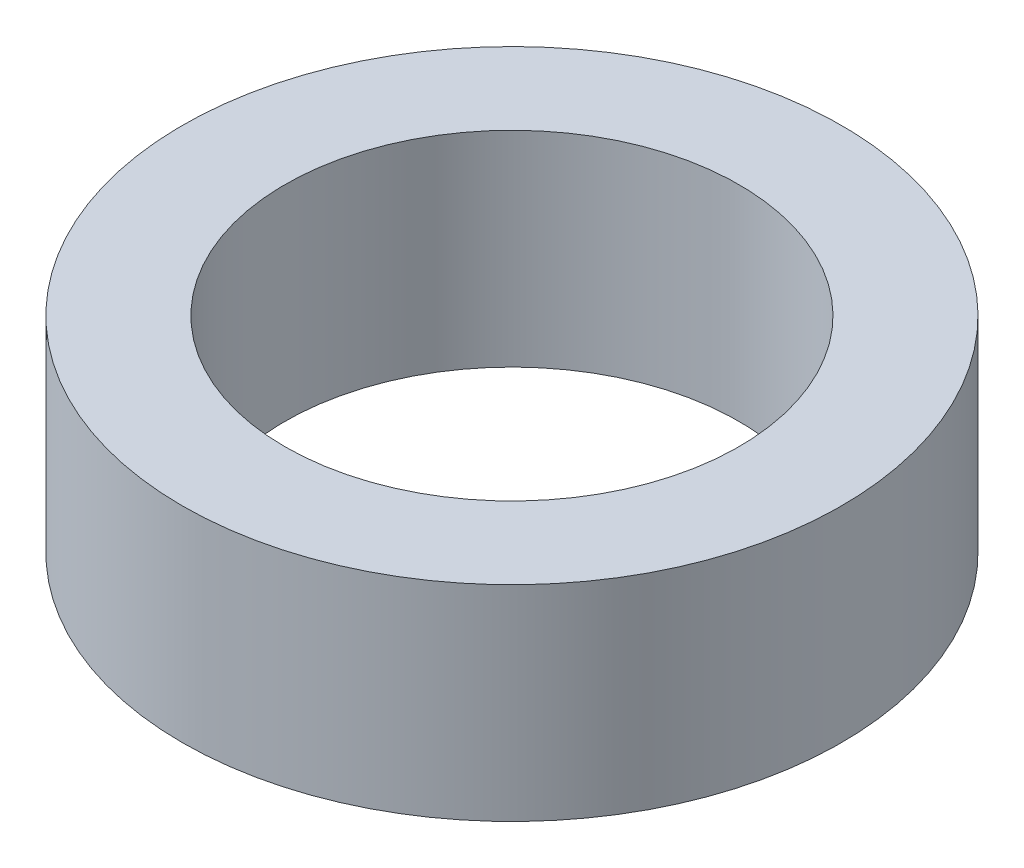
SolidWorks part; units mm, degrees
ref_plane "Front Plane" through (0, 0, 0) normal (0, 0, 1) x (1, 0, 0)
ref_plane "Top Plane" through (0, 0, 0) normal (0, 1, 0) x (1, 0, 0)
ref_plane "Right Plane" through (0, 0, 0) normal (1, 0, 0) x (0, 0, -1)
sketch "Axle Tension Bearing" plane through (0, 0, 0) normal (0, 1, 0) x (1, 0, 0)
  circle A0 centre (0, 0) radius 7.0301
  circle A1 centre (0, 0) radius 10.2051
  dimension "D1" = 14.0603
  dimension "D2" = 20.4103
extrude "Boss-Extrude1" add sketch "Axle Tension Bearing" along normal blind 6.35 contours A1 A0 region at (-9.9165, 0, 0)
equation "\"Ball Diameter\"= 1.75in"
equation "\"Sheet Thickness\"= 0.25in"
equation "\"Screw Diameter\"= .17in"
equation "\"Robot Diameter\"= 14in"
equation "\"Castor Screw Diameter\"= 0.22in"
equation "\"Wheel Diameter\" = 4in"
equation "\"Nut Diameter\" = 8.4mm"
equation "\"Nut Height\" = 2.9mm"
equation "\"Screw Height\" = 0.55in"
equation "\"Pulley Diameter\" = 1in"
equation "\"Reactor Height\" = 14in"
equation "\"Elevator Height\" = 11.5in"
equation "\"Elevator Width\" = \"Ball Diameter\" + 0.25in"
equation "\"Elevator Bearing Diameter\" = sqr(2*(\"Sheet Thickness\"^2)) + 0.2in"
equation "\"Elevator Axle Endcap Diameter\" = \"Pulley Diameter\" + 0.25in"
equation "\"Elevator Axle Length\" = \"Elevator Width\" + 8*\"Sheet Thickness\""
equation "\"D1@Axle Tension Bearing\"=\"Elevator Bearing Diameter\""
equation "\"D2@Axle Tension Bearing\"=\"Elevator Bearing Diameter\"+\"Sheet Thickness\""
equation "\"D1@Boss-Extrude1\"=\"Sheet Thickness\""
